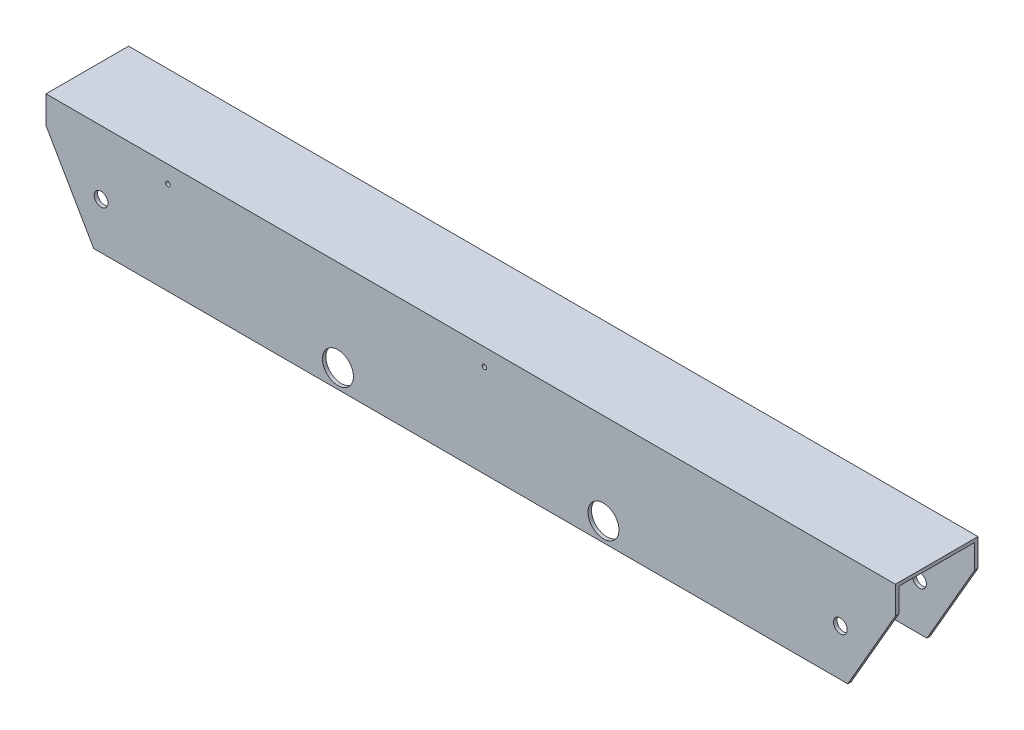
SolidWorks part; units mm, degrees
ref_plane "Front Plane" through (0, 0, 0) normal (0, 0, 1) x (1, 0, 0)
ref_plane "Top Plane" through (0, 0, 0) normal (0, 1, 0) x (1, 0, 0)
ref_plane "Right Plane" through (0, 0, 0) normal (1, 0, 0) x (0, 0, -1)
sketch "Sketch1" plane through (0, 0, 0) normal (1, 0, 0) x (0, 0, -1)
  line L0 (-34.925, 47.625) -> (-34.925, -47.625) construction
  line L1 (-38.1, 50.8) -> (38.1, 50.8)
  line L2 (-38.1, 50.8) -> (-38.1, -50.8)
  line L3 (-38.1, -50.8) -> (-34.925, -50.8)
  line L4 (38.1, 50.8) -> (38.1, -50.8)
  line L5 (-38.1, 50.8) -> (38.1, -50.8) construction
  line L6 (-38.1, -50.8) -> (38.1, 50.8) construction
  line L7 (34.925, 47.625) -> (34.925, -50.8)
  line L8 (-34.925, 47.625) -> (34.925, 47.625)
  line L9 (-34.925, 47.625) -> (-34.925, -50.8)
  line L10 (-34.925, -47.625) -> (34.925, -47.625) construction
  line L11 (34.925, 47.625) -> (34.925, -47.625) construction
  line L12 (-38.1, -50.8) -> (38.1, -50.8) construction
  line L13 (38.1, -50.8) -> (34.925, -50.8)
  point P0 (0, 0)
  dimension "D1" = 76.2
  dimension "D2" = 101.6
  dimension "D3" = 3.175
extrude "Boss-Extrude1" add sketch "Sketch1" along normal mid plane 783.7315
sketch "Sketch2" plane through (0, 0, 38.1) normal (0, 0, 1) x (1, 0, 0)
  line L1 (-391.8658, 50.8) -> (-391.8658, -50.8) construction
  line L8 (391.8658, -50.8) -> (-391.8658, -50.8) construction
  line L9 (0, -41.91) -> (0, 41.91) construction
  line L13 (0, 50.8) -> (0, -55.872) construction
  line L14 (391.8658, 50.8) -> (-391.8658, 50.8) construction
  circle A0 centre (-341.0658, -7.9375) radius 6.35
  circle A1 centre (122.5118, -33.3375) radius 14.2875
  circle A2 centre (341.0658, -7.9375) radius 6.35
  circle A4 centre (12.7, 34.925) radius 2.0828
  circle A5 centre (-279.4, 34.925) radius 2.0828
  circle A6 centre (-122.5118, -33.3375) radius 14.2875
  dimension "D1" = 122.5118
  dimension "D2" = 17.4625
  dimension "D3" = 220.025
  dimension "D4" = 218.5539
  dimension "D5" = 28.575
  dimension "D6" = 25.4
  dimension "D7" = 12.7
  dimension "D8" = 50.8
  dimension "D9" = 28.575
  dimension "D10" = 12.7
  dimension "D11" = 220.025
  dimension "D12" = 25.4
  dimension "D13" = 17.4625
  dimension "D22" = 15.875
  dimension "D23" = 15.875
  dimension "D24" = 112.4658
extrude "Cut-Extrude1" cut sketch "Sketch2" against normal blind 141.732
sketch "Sketch13" [suppressed] plane through (0, 0, 38.1) normal (0, 0, -1) x (-1, 0, 0)
  line L0 (-391.8658, -50.8) -> (391.8658, -50.8) construction
  line L2 (-25.4, 22.225) -> (0, 22.225)
  line L3 (-25.4, 22.225) -> (-25.4, 47.625)
  line L4 (-25.4, 47.625) -> (0, 47.625)
  line L5 (0, 22.225) -> (0, 47.625)
  line L6 (-25.4, 22.225) -> (0, 47.625) construction
  line L7 (-25.4, 47.625) -> (0, 22.225) construction
  line L8 (266.7, 22.225) -> (292.1, 22.225)
  line L9 (266.7, 22.225) -> (266.7, 47.625)
  line L10 (266.7, 47.625) -> (292.1, 47.625)
  line L11 (292.1, 22.225) -> (292.1, 47.625)
  line L12 (266.7, 22.225) -> (292.1, 47.625) construction
  line L13 (266.7, 47.625) -> (292.1, 22.225) construction
  circle A0 centre (-160.6118, -35.1235) radius 3.302
  circle A1 centre (-122.5118, -33.3375) radius 14.2875 construction
  circle A2 centre (-160.6118, 41.0765) radius 3.302
  circle A3 centre (-84.4118, 41.0765) radius 3.302
  circle A4 centre (-84.4118, -35.1235) radius 3.302
  point P12 (-12.7, 34.925)
  point P18 (279.4, 34.925)
  dimension "D1" = 6.604
  dimension "D2" = 15.6765
  dimension "D3" = 38.1
  dimension "D4" = 76.2
  dimension "D5" = 76.2
  dimension "D6" = 76.2
  dimension "D7" = 38.1
  dimension "D8" = 15.6765
  dimension "D9" = 25.4
  dimension "D10" = 25.4
  dimension "D11" = 25.4
  dimension "D12" = 25.4
extrude "Cut-Extrude11" [suppressed] cut sketch "Sketch13" along normal blind 33.2436
sketch "Sketch14" plane through (0, 0, -38.1) normal (0, 0, -1) x (-1, 0, 0)
  line L0 (-391.8658, -50.8) -> (391.8658, -50.8) construction
  line L2 (-25.4, 22.225) -> (0, 22.225)
  line L3 (-25.4, 22.225) -> (-25.4, 47.625)
  line L4 (-25.4, 47.625) -> (0, 47.625)
  line L5 (0, 22.225) -> (0, 47.625)
  line L6 (-25.4, 22.225) -> (0, 47.625) construction
  line L7 (-25.4, 47.625) -> (0, 22.225) construction
  line L8 (266.7, 22.225) -> (292.1, 22.225)
  line L9 (266.7, 22.225) -> (266.7, 47.625)
  line L10 (266.7, 47.625) -> (292.1, 47.625)
  line L11 (292.1, 22.225) -> (292.1, 47.625)
  line L12 (266.7, 22.225) -> (292.1, 47.625) construction
  line L13 (266.7, 47.625) -> (292.1, 22.225) construction
  circle A0 centre (-160.6118, -35.1235) radius 3.302
  circle A1 centre (-160.6118, 41.0765) radius 3.302
  circle A2 centre (-84.4118, 41.0765) radius 3.302
  circle A3 centre (-84.4118, -35.1235) radius 3.302
  circle A4 centre (-122.5118, -33.3375) radius 14.2875 construction
  point P12 (-12.7, 34.925)
  point P18 (279.4, 34.925)
  dimension "D1" = 6.604
  dimension "D2" = 15.6765
  dimension "D3" = 76.2
  dimension "D4" = 76.2
  dimension "D5" = 76.2
  dimension "D6" = 38.1
  dimension "D7" = 25.4
  dimension "D8" = 25.4
  dimension "D9" = 25.4
  dimension "D10" = 25.4
extrude "Cut-Extrude12" cut sketch "Sketch14" against normal blind 23.114
sketch "Sketch16" plane through (0, 0, 38.1) normal (0, 0, 1) x (1, 0, 0)
  line L1 (-391.8658, 50.8) -> (-391.8658, -50.8) construction
  line L2 (-391.8658, 25.4) -> (-347.8717, -50.8)
  line L3 (391.8658, -50.8) -> (-391.8658, -50.8) construction
  line L4 (-347.8717, -50.8) -> (-391.8658, -50.8)
  line L5 (-391.8658, -50.8) -> (-391.8658, 25.4)
  line L6 (0, 50.8) -> (0, -65.171) construction
  line L7 (0, -41.91) -> (0, 41.91) construction
  line L9 (347.8717, -50.8) -> (391.8658, -50.8)
  line L10 (391.8658, -50.8) -> (391.8658, 25.4)
  line L11 (391.8658, 25.4) -> (347.8717, -50.8)
  dimension "D1" = 60
  dimension "D2" = 76.2
  dimension "D4" = 43.9941
extrude "Cut-Extrude13" cut sketch "Sketch16" against normal blind 101.6
